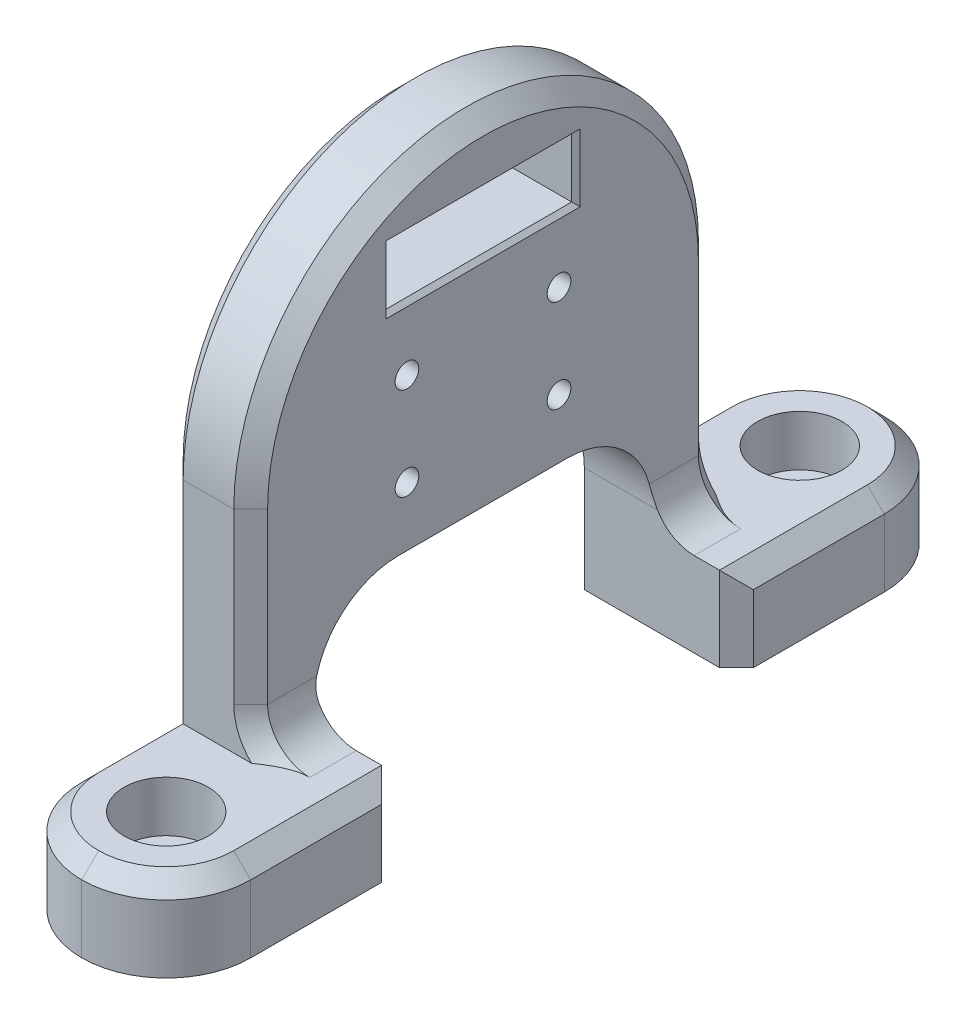
SolidWorks part; units mm, degrees
ref_plane "Front" through (0, 0, 0) normal (0, 0, 1) x (1, 0, 0)
ref_plane "Top" through (0, 0, 0) normal (0, 1, 0) x (1, 0, 0)
ref_plane "Right" through (0, 0, 0) normal (1, 0, 0) x (0, 0, -1)
sketch "草图1" plane through (0, 0, 0) normal (1, 0, 0) x (0, 0, -1)
  line L0 (-27.5, 0) -> (-27.5, -65)
  line L1 (-27.5, -65) -> (27.5, -65)
  line L2 (27.5, -65) -> (27.5, 0)
  arc A0 (27.5, 0) -> (-27.5, 0) centre (0, 0) ccw
  circle A1 centre (0, 0) radius 22 construction
extrude "凸台-拉伸1" add sketch "草图1" along normal blind 10
sketch "草图2" plane through (10, 0, 0) normal (1, 0, 0) x (0, 0, -1)
  line L1 (-9, -5.5) -> (9, -5.5) construction
  line L2 (-9, -5.5) -> (-9, 5.5) construction
  line L3 (-9, 5.5) -> (9, 5.5) construction
  line L4 (9, -5.5) -> (9, 5.5) construction
  line L5 (-9, -5.5) -> (9, 5.5) construction
  line L6 (-9, 5.5) -> (9, -5.5) construction
  circle A0 centre (-9, 5.5) radius 1.4
  circle A1 centre (9, 5.5) radius 1.4
  circle A2 centre (9, -5.5) radius 1.4
  circle A3 centre (-9, -5.5) radius 1.4
  point P0 (0, 0)
extrude "切除-拉伸1" cut sketch "草图2" against normal through all
sketch "草图4" plane through (0, 0, 0) normal (-1, 0, 0) x (0, 0, 1)
  line L1 (-11, 20) -> (11, 20)
  line L2 (-11, 20) -> (-11, 13)
  line L3 (-11, 13) -> (11, 13)
  line L4 (11, 20) -> (11, 13)
  line L5 (0, 13) -> (0, 20) construction
  line L6 (-11, 16.5) -> (11, 16.5) construction
  circle A0 centre (9, 5.5) radius 1.4 construction
  point P100 (0, 16.5)
  dimension "D1" = 22
  dimension "D2" = 7
  dimension "D3" = 0
  dimension "D4" = 11
extrude "切除-拉伸4" cut sketch "草图4" against normal blind 10
chamfer "倒角2" distance 0.5 angle 45 8 edges at (0, 16.5, 11) (0, 20, 0) (0, 16.5, -11) (0, 13, 0) (10, 16.5, 11) (10, 20, 0) (10, 16.5, -11) (10, 13, 0)
sketch "草图5" plane through (0, -65, 0) normal (0, -1, 0) x (-1, 0, 0)
  line L1 (0, -27.5) -> (-10, -27.5)
  line L2 (0, -27.5) -> (0, 27.5)
  line L3 (0, 27.5) -> (-10, 27.5)
  line L4 (-10, -27.5) -> (-10, 27.5)
  line L5 (-5, 27.5) -> (-5, -27.5) construction
  line L6 (0, 0) -> (-10, 0) construction
  point P92 (-5, 0)
extrude "切除-拉伸5" cut sketch "草图5" against normal blind 40
sketch "草图6" plane through (0, -25, 0) normal (0, -1, 0) x (-1, 0, 0)
  line L2 (0, -27.5) -> (0, 27.5)
  line L4 (-20, -27.5) -> (-20, 27.5)
  line L5 (-10, 27.5) -> (-10, -27.5) construction
  line L6 (0, 0) -> (-20, 0) construction
  line L12 (0, -27.5) -> (0, -47.5)
  line L13 (0, -47.5) -> (-20, -47.5)
  line L14 (-20, -27.5) -> (-20, -47.5)
  line L15 (-10, -47.5) -> (-10, -27.5) construction
  line L16 (0, -37.5) -> (-20, -37.5) construction
  line L18 (0, 27.5) -> (0, 47.5)
  line L19 (0, 47.5) -> (-20, 47.5)
  line L20 (-20, 27.5) -> (-20, 47.5)
  line L21 (-10, 47.5) -> (-10, 27.5) construction
  line L22 (0, 37.5) -> (-20, 37.5) construction
  point P114 (-10, 37.5)
  point P141 (-10, -37.5)
  point P240 (-10, 0)
extrude "凸台-拉伸2" add sketch "草图6" along normal blind 10
fillet "圆角1" radius 10 4 edges at (0, -30, -47.5) (20, -30, -47.5) (0, -30, 47.5) (20, -30, 47.5)
sketch "草图7" plane through (0, -25, 0) normal (0, 1, 0) x (1, 0, 0)
  circle A0 centre (10, 37.5) radius 5
  circle A1 centre (10, -37.5) radius 5
extrude "切除-拉伸6" cut sketch "草图7" against normal blind 6
sketch "草图8" plane through (0, -31, 0) normal (0, 1, 0) x (1, 0, 0)
  circle A0 centre (10, 37.5) radius 3.1
  circle A1 centre (10, -37.5) radius 3.1
extrude "切除-拉伸7" cut sketch "草图8" against normal blind 6
sketch "草图9" plane through (0, 0, 0) normal (-1, 0, 0) x (0, 0, 1)
  line L0 (37.5, -35) -> (-37.5, -35) construction
  line L1 (-20, -57.5) -> (20, -57.5)
  line L2 (-20, -57.5) -> (-20, -12.5)
  line L3 (-20, -12.5) -> (20, -12.5)
  line L4 (20, -57.5) -> (20, -12.5)
  line L5 (-20, -57.5) -> (20, -12.5) construction
  line L6 (-20, -12.5) -> (20, -57.5) construction
  point P0 (0, -35)
extrude "切除-拉伸8" cut sketch "草图9" against normal through all
fillet "圆角2" radius 10 2 edges at (5, -12.5, -20) (5, -12.5, 20)
fillet "圆角3" radius 5 2 edges at (10, -25, -23.75) (10, -25, 23.75)
chamfer "倒角3" distance 2 angle 45 23 edges at (0, -25, 32.5) (20, -25, -28.75) (17.0711, -25, 44.5711) (2.9289, -25, 44.5711) (17.0711, -25, -44.5711) (2.9289, -25, -44.5711) (20, -25, 28.75) (0, -28.75, 20) (20, -30, 20) (20, -30, -20) (0, -28.75, -20) (0, -12.5, 0) (0, -15.4289, -17.0711) (0, -15.4289, 17.0711) (10, -10, -27.5) (11.4645, -23.5355, -27.5) (11.4645, -23.5355, 27.5) (10, 27.5, 0) (0, -12.5, 27.5) (0, 27.5, 0) (0, -12.5, -27.5) (10, -10, 27.5) (0, -25, -32.5)
